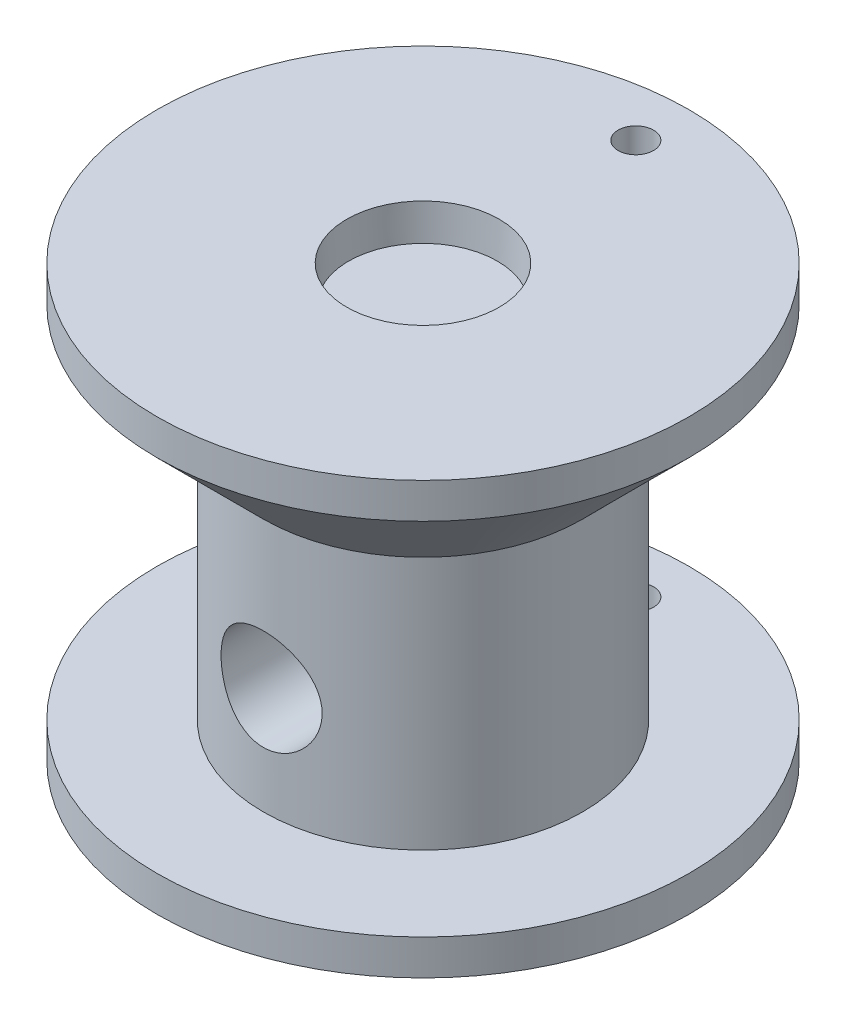
SolidWorks part; units mm, degrees
material "ABS"
ref_plane "Front Plane" through (0, 0, 0) normal (0, 0, 1) x (1, 0, 0)
ref_plane "Top Plane" through (0, 0, 0) normal (0, 1, 0) x (1, 0, 0)
ref_plane "Right Plane" through (0, 0, 0) normal (1, 0, 0) x (0, 0, -1)
sketch "Sketch1" plane through (0, 0, 0) normal (1, 0, 0) x (0, 0, -1)
  line L0 (0, 6.075) -> (-7.5, 6.075) construction
  line L1 (0, 0) -> (0, 18.3424) construction
  line L2 (-7.5, 6.075) -> (-7.5, -6.075) construction
  line L3 (-7.5, -6.075) -> (0, -6.075) construction
  line L4 (0, -6.075) -> (0, 6.075) construction
  line L5 (-7.5, 6.075) -> (-7.5, 5.075)
  line L7 (-4.5, 2.075) -> (-4.5, -5.075)
  line L9 (-7.5, -5.075) -> (-7.5, -6.075)
  line L10 (-7.5, -6.075) -> (0, -6.075) construction
  line L11 (0, -6.075) -> (0, 6.075) construction
  line L12 (0, 6.075) -> (-7.5, 6.075) construction
  line L13 (-7.5, 5.075) -> (-4.5, 2.075)
  line L14 (-4.5, 2.075) -> (-4.5, 6.075) construction
  line L15 (-7.5, -5.075) -> (-4.5, -5.075)
  line L16 (-7.5, 6.075) -> (-2.15, 6.075)
  line L17 (2.15, -6.075) -> (-2.15, -6.075) construction
  line L18 (2.15, -6.075) -> (2.15, 6.075) construction
  line L19 (2.15, 6.075) -> (-2.15, 6.075) construction
  line L20 (-2.15, -6.075) -> (-2.15, 6.075) construction
  line L21 (2.15, -6.075) -> (-2.15, 6.075) construction
  line L22 (2.15, 6.075) -> (-2.15, -6.075) construction
  line L23 (-2.1, 5.075) -> (2.1, 5.075) construction
  line L24 (-2.1, 5.075) -> (-2.1, 7.075) construction
  line L25 (-2.1, 7.075) -> (2.1, 7.075) construction
  line L26 (2.1, 5.075) -> (2.1, 7.075) construction
  line L27 (-2.1, 5.075) -> (2.1, 7.075) construction
  line L28 (-2.1, 7.075) -> (2.1, 5.075) construction
  line L29 (-2.15, 6.075) -> (-2.1, 5.075)
  line L30 (-2.1, 5.075) -> (0, 5.075)
  line L31 (0, 5.075) -> (0, -6.075) construction
  line L33 (-2.15, 1.925) -> (-2.15, -6.075)
  line L34 (-2.15, -6.075) -> (-7.5, -6.075)
  line L35 (-2.15, 1.925) -> (0, 4.075)
  line L36 (0, 4.075) -> (0, 5.075)
  point P3 (0, 0)
  point P16 (0, 0)
  dimension "D1" = 15
  dimension "D2" = 8
  dimension "D3" = 45
  dimension "D4" = 1
  dimension "D5" = 3
  dimension "D6" = 4.3
  dimension "D7" = 2.35
  dimension "D8" = 4.2
  dimension "D9" = 1
  dimension "D10" = 45
revolve "Revolve1" add sketch "Sketch1" angle 360 about L1
sketch "Sketch2" plane through (0, -6.075, 0) normal (0, -1, 0) x (1, 0, 0)
  line L0 (1.6733, 1.35) -> (-1.6733, 1.35)
  circle A2 centre (0, 0) radius 2.15 construction
  circle A3 centre (0, 0) radius 2.15 construction
  arc A4 (1.6733, 1.35) -> (-1.6733, 1.35) centre (0, 0) ccw
  point P0 (0, -2.15)
  point P3 (0, 1.35)
  dimension "D1" = 3.5
extrude "Boss-Extrude1" add sketch "Sketch2" against normal up to next
sketch "Sketch5" plane through (0, -5.075, 0) normal (0, 1, 0) x (1, 0, 0)
  line L0 (0, 4.5) -> (0, 7.5) construction
  circle A0 centre (0, 6) radius 0.5
  circle A1 centre (0, 0) radius 4.5 construction
  circle A2 centre (0, 0) radius 7.5 construction
  point P9 (0, 0)
  dimension "D1" = 1
extrude "Cut-Extrude1" cut sketch "Sketch5" against normal through all both and the other way through all
sketch "Sketch6" plane through (0, 0, 1.35) normal (0, 0, -1) x (-1, 0, 0)
  line L0 (0, -6.075) -> (0, 1.925) construction
  line L1 (1.6733, -6.075) -> (-1.6733, -6.075) construction
  circle A0 centre (0, -2.075) radius 1.425
  dimension "D2" = 2.85
  dimension "D1" = 8
extrude "Cut-Extrude2" cut sketch "Sketch6" against normal through all both and the other way through all
